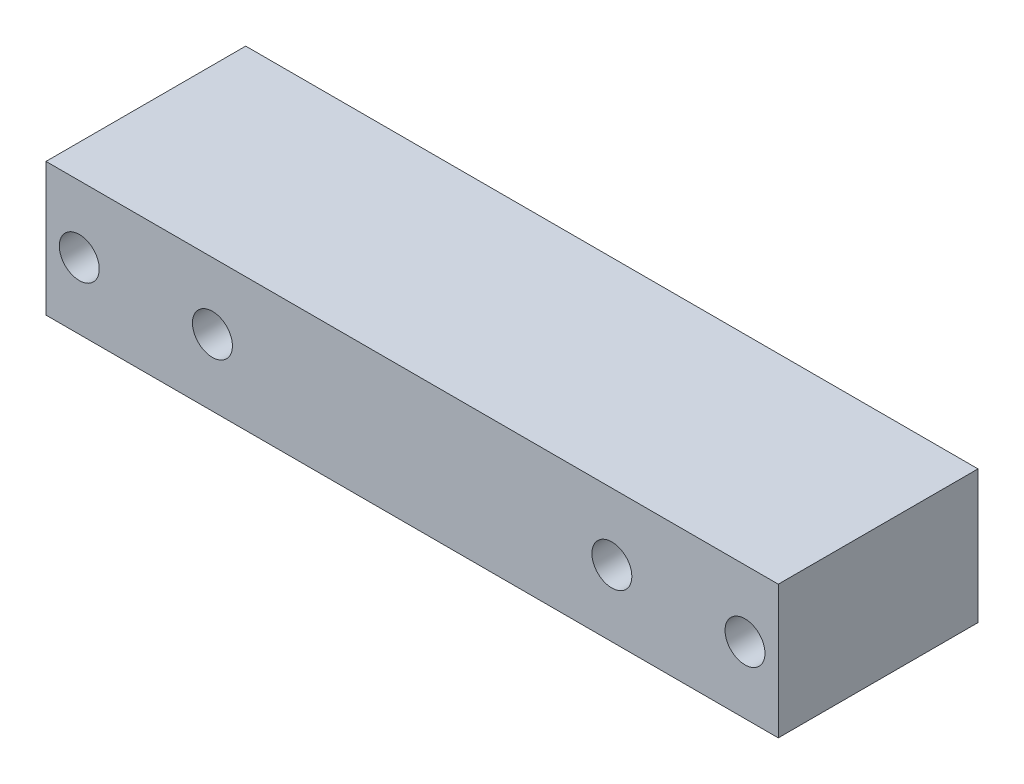
SolidWorks part; units mm, degrees
ref_plane "Front Plane" through (0, 0, 0) normal (0, 0, 1) x (1, 0, 0)
ref_plane "Top Plane" through (0, 0, 0) normal (0, 1, 0) x (1, 0, 0)
ref_plane "Right Plane" through (0, 0, 0) normal (1, 0, 0) x (0, 0, -1)
sketch "Sketch1" plane through (0, 0, 0) normal (0, 0, 1) x (1, 0, 0)
  line L1 (0, 0) -> (-55, 0)
  line L2 (0, 0) -> (0, 10)
  line L3 (0, 10) -> (-55, 10)
  line L4 (-55, 0) -> (-55, 10)
  circle A4 centre (-2.5, 5) radius 1.5
  circle A5 centre (-12.5, 5) radius 1.5
  circle A6 centre (-42.5, 5) radius 1.5
  circle A7 centre (-52.5, 5) radius 1.5
extrude "Boss-Extrude1" add sketch "Sketch1" along normal blind 15
